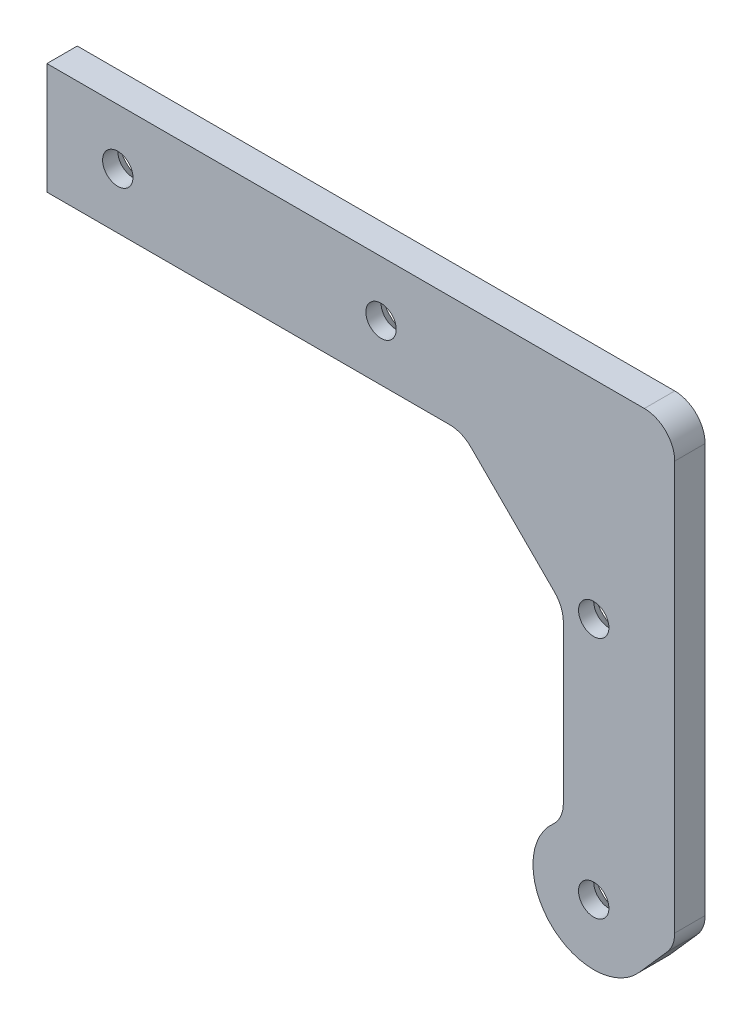
SolidWorks part; units mm, degrees
ref_plane "Спереди" through (0, 0, 0) normal (0, 0, 1) x (1, 0, 0)
ref_plane "Сверху" through (0, 0, 0) normal (0, 1, 0) x (1, 0, 0)
ref_plane "Справа" through (0, 0, 0) normal (1, 0, 0) x (0, 0, -1)
sketch "Эскиз1" plane through (0, 0, 0) normal (0, 0, 1) x (1, 0, 0)
  line L0 (-56.5, 0) -> (5.5, 0) construction
  line L1 (-2.5, 5.5) -> (-2.5, -46.5) construction
  line L2 (-56.5, 5.5) -> (-56.5, -5.5)
  line L3 (-56.5, -5.5) -> (-15.5, -5.5)
  line L4 (-5.5, -46.5) -> (5.5, -46.5) construction
  line L5 (-5.5, -15.5) -> (-5.5, -33.8038)
  line L6 (5.5, -39) -> (5.5, 5.5)
  line L7 (5.5, 5.5) -> (-56.5, 5.5)
  line L8 (-15.5, -5.5) -> (-5.5, -15.5)
  line L9 (0, 5.5) -> (0, -46.5) construction
  line L10 (2, -42.9686) -> (5.5, -39)
  line L11 (-5.5, -44.1962) -> (-5.5, -46.5) construction
  line L12 (5.5, -39) -> (5.5, -46.5) construction
  arc A0 (-5.5, -33.8038) -> (2, -42.9686) centre (-2.5, -39) ccw
  circle A4 centre (-23.5, 0) radius 1.5
  circle A5 centre (-49.5, 0) radius 1.5
  circle A6 centre (-2.5, -15) radius 1.5
  circle A7 centre (-2.5, -39) radius 1.5
  dimension "D4" = 11
  dimension "D7" = 15
  dimension "D12" = 3
  dimension "D10" = 12
  dimension "D1" = 11
  dimension "D2" = 51
  dimension "D3" = 52
  dimension "D5" = 10
  dimension "D6" = 45
  dimension "D8" = 3
  dimension "D9" = 21
  dimension "D14" = 26
  dimension "D16" = 24
extrude "тело" add sketch "Эскиз1" along normal blind 3
fillet "Fillet1" radius 3 5 edges at (5.5, 5.5, 1.5) (5.5, -39, 1.5) (-5.5, -33.8038, 1.5) (-5.5, -15.5, 1.5) (-15.5, -5.5, 1.5)
chamfer "Фаски под шляпки (левая)" distance 1.5 angle 45 4 edges at (-48, 0, 0) (-22, 0, 0) (-1, -15, 0) (-1, -39, 0)
chamfer "Фаски под шляпки (правая)" [suppressed] distance 1.5 angle 45
